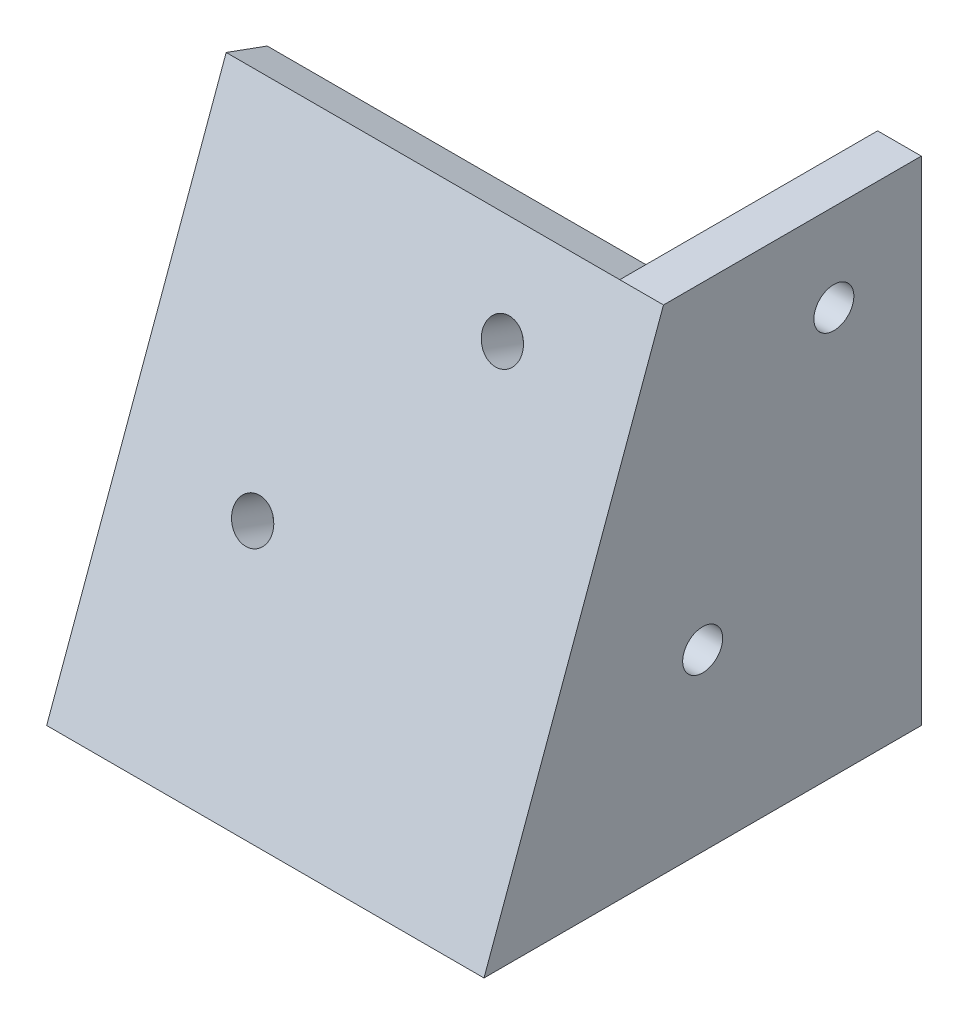
SolidWorks part; units mm, degrees
material "ABS"
ref_plane "Front Plane" through (0, 0, 0) normal (0, 0, 1) x (1, 0, 0)
ref_plane "Top Plane" through (0, 0, 0) normal (0, 1, 0) x (1, 0, 0)
ref_plane "Right Plane" through (0, 0, 0) normal (1, 0, 0) x (0, 0, -1)
sketch "Sketch1" plane through (0, 0, 0) normal (1, 0, 0) x (0, 0, -1)
  line L0 (0, 0) -> (-50, 0)
  line L1 (-50, 0) -> (-29.4788, 56.3816)
  line L2 (-29.4788, 56.3816) -> (-24.7803, 54.6715)
  line L3 (-24.7803, 54.6715) -> (-42.8593, 5)
  line L4 (-42.8593, 5) -> (0, 5)
  line L5 (0, 5) -> (0, 0)
  dimension "D1" = 60
  dimension "D2" = 50
  dimension "D3" = 70
  dimension "D4" = 5
  dimension "D5" = 5
extrude "Main" add sketch "Sketch1" along normal mid plane 50
sketch "Sketch2" plane through (0, 0, 0) normal (0, 0, -1) x (-1, 0, 0)
  line L0 (-25, 56.3816) -> (25, 56.3816) construction
  line L1 (-25, 0) -> (-20, 0)
  line L2 (-25, 0) -> (-25, 56.3816)
  line L3 (-25, 56.3816) -> (-20, 56.3816)
  line L4 (-20, 0) -> (-20, 56.3816)
  dimension "D1" = 5
extrude "Back" add sketch "Sketch2" against normal up to next
hole_wizard "Base Holes" positions "3DSketch4" profile "Sketch5" hole size "#8" standard "ANSI Inch"
sketch3d "3DSketch4"
  line L0 (-25, 5, 0) -> (-25, 5, 42.8593) construction
  line L3 (20, 5, 0) -> (-25, 5, 0) construction
  point P0 (10, 5, 20)
  point P2 (-10, 5, 20)
  dimension "D1" = 15
  dimension "D2" = 15
  dimension "D3" = 20
  dimension "D4" = 20
sketch "Sketch5" plane through (10, 5, 20) normal (1, 0, 0) x (0, 0, 1)
  line L0 (0, 0) -> (0, 5)
  line L1 (0, 5) -> (2.286, 5)
  line L2 (2.286, 5) -> (2.286, 0)
  line L5 (2.286, 0) -> (0, 0)
  line L10 (0, 5) -> (-2.286, 5) construction
  line L11 (0, -6.35) -> (0, 107.95) construction
  dimension "Hole Dia." = 4.572
  dimension "Hole Depth" = 5
  dimension "Drill Angle" = 180
hole_wizard "BackPanelHoles" positions "Sketch6" profile "Sketch7" hole size "#8" standard "ANSI Inch"
sketch "Sketch6" plane through (20, 0, 0) normal (-1, 0, 0) x (0, 0, 1)
  line L0 (29.4788, 56.3816) -> (0, 56.3816) construction
  line L1 (0, 5) -> (0, 56.3816) construction
  line L2 (50, 0) -> (0, 0) construction
  point P0 (10, 46.3816)
  point P2 (25, 20)
  dimension "D1" = 10
  dimension "D2" = 10
  dimension "D3" = 20
  dimension "D4" = 25
sketch "Sketch7" plane through (20, 46.3816, 10) normal (0, 1, 0) x (0, 0, 1)
  line L0 (0, 0) -> (0, 5)
  line L1 (0, 5) -> (2.286, 5)
  line L2 (2.286, 5) -> (2.286, 0)
  line L5 (2.286, 0) -> (0, 0)
  line L10 (0, 5) -> (-2.286, 5) construction
  line L11 (0, -6.35) -> (0, 107.95) construction
  dimension "Hole Dia." = 4.572
  dimension "Hole Depth" = 5
  dimension "Drill Angle" = 180
hole_wizard "SidePanelHoles" positions "3DSketch5" profile "Sketch8" hole size "#8" standard "ANSI Inch"
sketch3d "3DSketch5"
  line L0 (25, 56.3816, 29.4788) -> (25, 0, 50) construction
  line L1 (20, 56.3816, 29.4788) -> (-25, 56.3816, 29.4788) construction
  line L2 (25, 0, 50) -> (-25, 0, 50) construction
  line L3 (-25, 56.3816, 29.4788) -> (-25, 0, 50) construction
  point P0 (10, 46.9846, 32.899)
  point P2 (-10, 23.4923, 41.4495)
  dimension "D1" = 15
  dimension "D2" = 10
  dimension "D3" = 25
  dimension "D4" = 15
  dimension "D5" = 50
  dimension "D6" = 35
sketch "Sketch8" plane through (10, 46.9846, 32.899) normal (1, 0, 0) x (0, -0.9397, 0.342)
  line L0 (0, 0) -> (0, 5)
  line L1 (0, 5) -> (2.286, 5)
  line L2 (2.286, 5) -> (2.286, 0)
  line L5 (2.286, 0) -> (0, 0)
  line L10 (0, 5) -> (-2.286, 5) construction
  line L11 (0, -6.35) -> (0, 107.95) construction
  dimension "Hole Dia." = 4.572
  dimension "Hole Depth" = 5
  dimension "Drill Angle" = 180
ref_plane "Midplane" through (0, 0, 0) normal (-1, 0, 0) x (0, 0, 1)
sketch "Sketch9" plane through (0, 5, 0) normal (0, 1, 0) x (1, 0, 0)
  line L0 (20, 0) -> (20, -42.8593) construction
  line L1 (-25, 0) -> (20, 0)
  line L2 (-25, 0) -> (-25, -5)
  line L3 (-25, -5) -> (20, -5)
  line L4 (20, 0) -> (20, -5)
  dimension "D1" = 5
extrude "Battery Cut" cut sketch "Sketch9" against normal up to next
